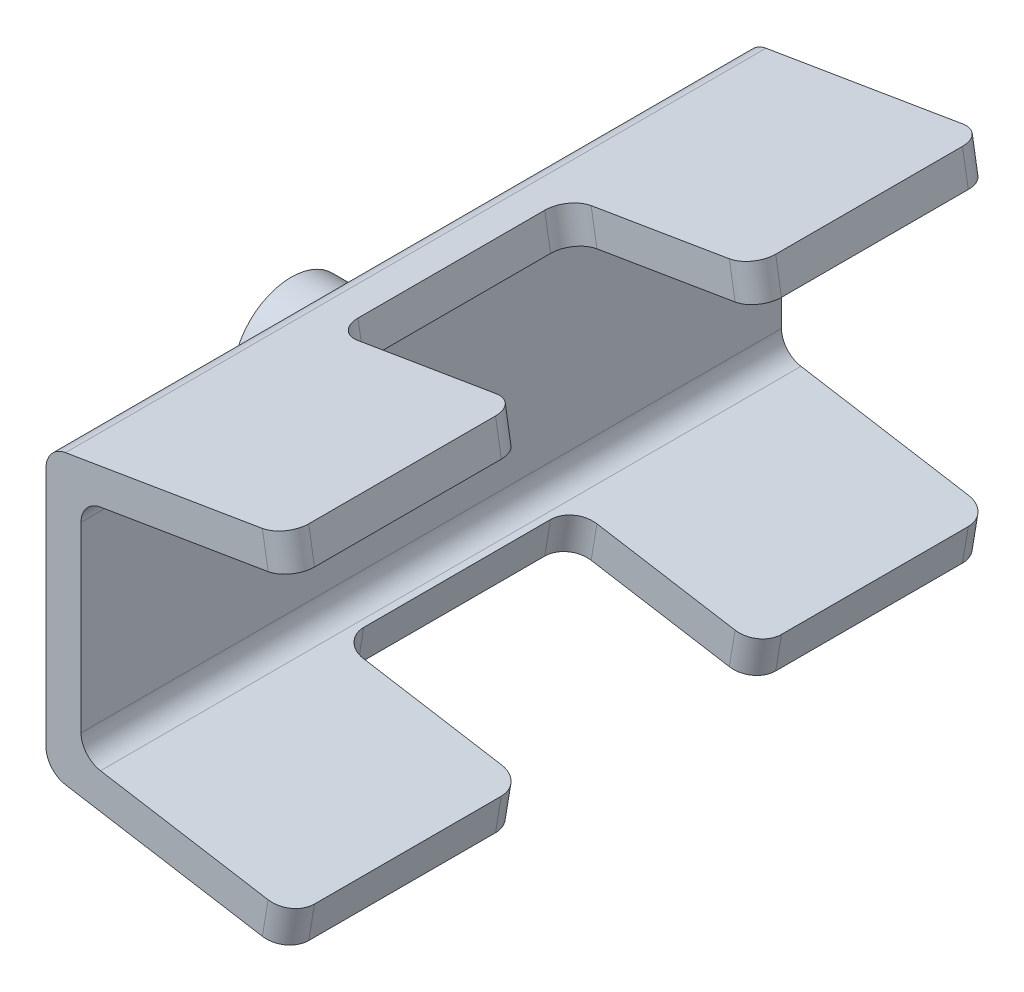
SolidWorks part; units mm, degrees
ref_plane "Front Plane" through (0, 0, 0) normal (0, 0, 1) x (1, 0, 0)
ref_plane "Top Plane" through (0, 0, 0) normal (0, 1, 0) x (1, 0, 0)
ref_plane "Right Plane" through (0, 0, 0) normal (1, 0, 0) x (0, 0, -1)
sketch "Sketch1" plane through (0, 0, 0) normal (1, 0, 0) x (0, 0, -1)
  circle A0 centre (0, 0) radius 63.5
  dimension "D1" = 127
extrude "Boss-Extrude1" add sketch "Sketch1" along normal mid plane 127
sketch "Sketch2" plane through (0, 0, 0) normal (0, 0, 1) x (1, 0, 0)
  line L11 (88.9, -120.65) -> (88.9, 120.65)
  line L15 (-63.5, 63.5) -> (-63.5, -63.5) construction
  line L16 (311.2364, 196.3316) -> (50.8, 152.9255)
  line L20 (317.5, 158.75) -> (88.9, 120.65)
  line L21 (88.9, -120.65) -> (317.5, -158.75)
  line L22 (50.8, -152.9255) -> (50.8, 152.9255)
  line L23 (50.8, -152.9255) -> (311.2364, -196.3316)
  line L24 (311.2364, -196.3316) -> (317.5, -158.75)
  line L25 (317.5, 158.75) -> (311.2364, 196.3316)
  point P3 (63.5, -177.8)
  point P7 (88.9, 0)
  point P13 (317.5, 0)
  point P14 (63.5, 177.8)
  dimension "D1" = 241.3
  dimension "D2" = 99.462
  dimension "D3" = 99.462
  dimension "D4" = 152.4
  dimension "D5" = 0
  dimension "D6" = 38.1
extrude "Boss-Extrude2" add sketch "Sketch2" along normal mid plane 762
sketch "Sketch3" plane through (334.6622, 55.777, 0) normal (0.9864, 0.1644, 0) x (0, 0, -1)
  line L0 (0, 104.3934) -> (-127, 104.3934)
  line L1 (-381, 104.3934) -> (381, 104.3934) construction
  line L2 (-381, 104.3934) -> (381, 104.3934) construction
  line L3 (0, 104.3934) -> (127, 104.3934)
  line L4 (127, 104.3934) -> (127, 142.4934)
  line L5 (-381, 142.4934) -> (381, 142.4934) construction
  line L6 (127, 142.4934) -> (-127, 142.4934)
  line L7 (-127, 142.4934) -> (-127, 104.3934)
  dimension "D1" = 127
  dimension "D2" = 127
extrude "Cut-Extrude1" cut sketch "Sketch3" against normal blind 203.2
sketch "Sketch4" plane through (334.6622, -55.777, 0) normal (0.9864, -0.1644, 0) x (0, 0, -1)
  line L0 (0, -142.4934) -> (-127, -142.4934)
  line L1 (-381, -142.4934) -> (381, -142.4934) construction
  line L2 (0, -142.4934) -> (127, -142.4934)
  line L3 (127, -142.4934) -> (127, -104.3934)
  line L4 (-381, -104.3934) -> (381, -104.3934) construction
  line L5 (127, -104.3934) -> (-127, -104.3934)
  line L6 (-381, -104.3934) -> (381, -104.3934) construction
  line L7 (-127, -104.3934) -> (-127, -142.4934)
  dimension "D1" = 127
  dimension "D2" = 127
extrude "Cut-Extrude2" cut sketch "Sketch4" against normal blind 203.2
fillet "Fillet1" radius 25.4 2 edges at (88.9, 120.65, 0) (88.9, -120.65, 0)
fillet "Fillet2" radius 25.4 2 edges at (50.8, -152.9255, 0) (50.8, 152.9255, 0)
fillet "Fillet3" radius 25.4 12 edges at (314.3682, -177.5408, -381) (314.3682, -177.5408, -127) (314.3682, -177.5408, 381) (314.3682, -177.5408, 127) (113.933, -144.1349, -127) (113.933, -144.1349, 127) (314.3682, 177.5408, -381) (314.3682, 177.5408, 381) (314.3682, 177.5408, -127) (314.3682, 177.5408, 127) (113.933, 144.1349, -127) (113.933, 144.1349, 127)
